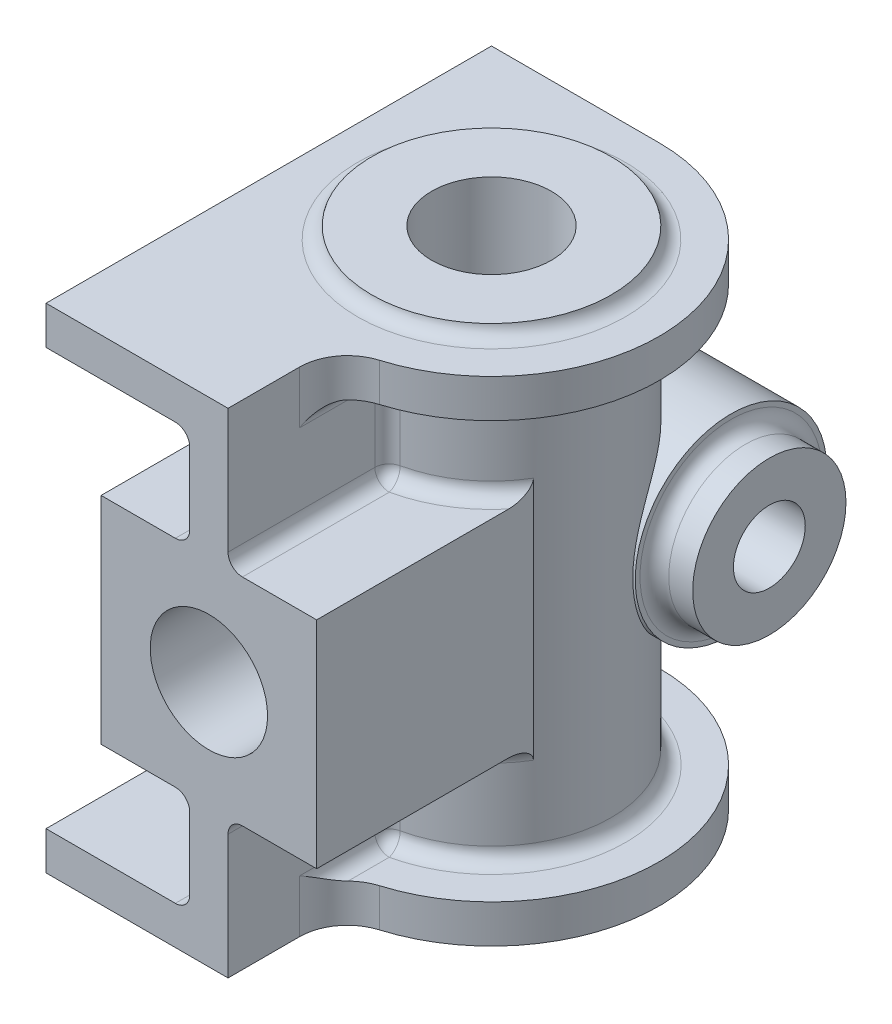
SolidWorks part; units mm, degrees
material "AISI 1020"
ref_plane "Front Plane" through (0, 0, 0) normal (1, 0, 0) x (0, 1, 0)
ref_plane "Top Plane" through (0, 0, 0) normal (0, 0, 1) x (0, 1, 0)
ref_plane "Right Plane" through (0, 0, 0) normal (0, 1, 0) x (-1, 0, 0)
sketch "Sketch1" plane through (0, 0, 0) normal (0, 1, 0) x (-1, 0, 0)
  line L0 (35, 0) -> (35, 58)
  line L1 (35, 58) -> (-3, 58)
  line L2 (35, 0) -> (35, -35)
  line L3 (0, -35) -> (35, -35)
  line L4 (-3, 58) -> (-3, 34.8712)
  line L5 (5, 58) -> (5, 34.641)
  circle A0 centre (0, 0) radius 12.5
  circle A1 centre (0, 0) radius 25
  circle A2 centre (0, 0) radius 35
  point P12 (5, 58)
  dimension "D1" = 25
  dimension "D2" = 50
  dimension "D3" = 70
  dimension "D4" = 58
  dimension "D5" = 38
  dimension "D6" = 8
extrude "Boss-Extrude1" add sketch "Sketch1" against normal blind 103 contours A2 A1 | A2 L0 L1 L5 | A2 L5 L1 L4 | A2 L3 L2 | A1 A0 region at (-21.9929, 0, 41.1744) region at (-24.0487, 0, -24.0487) region at (-27.1821, 0, -27.1821) region at (-1.0066, 0, 46.4544) region at (24.2929, 0, 0)
extrude "Boss-Extrude2" add sketch "Sketch1<4>" against normal blind 105.5 contours A1 A0 region at (24.2929, 0, 0)
sketch "Sketch1<4>" plane through (0, 0, 0) normal (0, 1, 0) x (-1, 0, 0) same geometry as "Sketch1"
extrude "Cut-Extrude1" cut sketch "Sketch1<6>" against normal blind 95 contours A2 L5 L1 L4 | A2 L0 L1 L5 | A2 L3 L2 | A2 A1 region at (-21.9929, 0, 41.1744) region at (-24.0487, 0, -24.0487) region at (-27.1821, 0, -27.1821) region at (-1.0066, 0, 46.4544)
sketch "Sketch1<6>" plane through (0, 0, 0) normal (0, 1, 0) x (-1, 0, 0) same geometry as "Sketch1"
extrude "Boss-Extrude3" add sketch "Sketch1<7>" against normal blind 8 contours A2 A1 | A2 L5 L1 L4 | A2 L0 L1 L5 | A2 L3 L2 region at (-21.9929, 0, 41.1744) region at (-24.0487, 0, -24.0487) region at (-27.1821, 0, -27.1821) region at (-1.0066, 0, 46.4544)
sketch "Sketch1<7>" plane through (0, 0, 0) normal (0, 1, 0) x (-1, 0, 0) same geometry as "Sketch1"
extrude "Boss-Extrude4" add sketch "Sketch1<8>" along normal blind 2.5 contours A1 A0 region at (24.2929, 0, 0)
sketch "Sketch1<8>" plane through (0, 0, 0) normal (0, 1, 0) x (-1, 0, 0) same geometry as "Sketch1"
sketch "Sketch2" plane through (0, 0, 58) normal (0, 0, 1) x (1, 0, 0)
  line L0 (-35, 0) -> (3, 0) construction
  line L1 (3, -103) -> (-5, -103)
  line L2 (3, -103) -> (3, 0)
  line L3 (3, 0) -> (-5, 0)
  line L4 (-5, -103) -> (-5, 0)
  line L5 (3, -51.5) -> (-5, -51.5) construction
  line L7 (21.5, -29) -> (-23.5, -29)
  line L8 (21.5, -29) -> (21.5, -74)
  line L9 (21.5, -74) -> (-23.5, -74)
  line L10 (-23.5, -29) -> (-23.5, -74)
  line L11 (21.5, -29) -> (-23.5, -74) construction
  line L12 (21.5, -74) -> (-23.5, -29) construction
  circle A0 centre (-1, -51.5) radius 11
  point P7 (-1, -51.5)
  line M11 (3, -95) -> (-35, -95)
  dimension "D4" = 22
  dimension "D1" = 8
  dimension "D2" = 45
  dimension "D3" = 45
extrude "Boss-Extrude6" add sketch "Sketch2" against normal up to next contours A0 L2 L9 L8 L7 | A0 L4 L9 L2 | A0 L4 L7 L10 L9 | L2 A0 L4 | L2 A0 | L4 A0 | A0 L2 L7 L4 | L2 L9 L4 M11 | L7 L2 L3 L4 region at (-1, -84.5, 58) region at (-1, -68.1241, 58) region at (13.1578, -51.5, 58) region at (-15.1578, -51.5, 58) region at (-1, -51.5, 58) region at (5.8939, -51.5, 58) region at (-7.8939, -51.5, 58) region at (-1, -34.8759, 58) region at (-1, -14.5, 58)
sketch "Sketch5" plane through (0, 0, 58) normal (0, 0, 1) x (1, 0, 0)
  point P0 (-1, -51.5)
hole_wizard "Tap Drill for M24 Helicoil1" positions "Sketch5" profile "Sketch6" hole size "M24x2.0" standard "BSI"
sketch "Sketch6" plane through (-1, -51.5, 58) normal (1, 0, 0) x (0, -1, 0)
  line L0 (0, 0) -> (0, 27.3605)
  line L1 (0, 27.3605) -> (12.25, 20)
  line L2 (12.25, 20) -> (12.25, 0)
  line L5 (12.25, 0) -> (0, 0)
  line L10 (0, 27.3605) -> (-12.25, 20) construction
  line L11 (0, -6.35) -> (0, 107.95) construction
  dimension "Hole Dia." = 24.5
  dimension "Hole Depth" = 20
  dimension "Drill Angle" = 118
sketch "Sketch9" plane through (0, 0, 58) normal (0, 0, 1) x (1, 0, 0)
  point P0 (-1, -51.5)
hole_wizard "Ø22.0 (22) Diameter Hole1" positions "Sketch9" profile "Sketch8" hole size "Ø22.0" standard "BSI"
sketch "Sketch8" plane through (-1, -51.5, 58) normal (1, 0, 0) x (0, -1, 0)
  line L0 (0, 0) -> (0, 38.6095)
  line L1 (0, 38.6095) -> (11, 32)
  line L2 (11, 32) -> (11, 0)
  line L5 (11, 0) -> (0, 0)
  line L10 (0, 38.6095) -> (-11, 32) construction
  line L11 (0, -6.35) -> (0, 107.95) construction
  dimension "Hole Dia." = 22
  dimension "Hole Depth" = 32
  dimension "Drill Angle" = 118
sketch "Sketch10" plane through (0, 0, 0) normal (1, 0, 0) x (0, 1, 0)
  line L0 (-95, -25) -> (-8, -25)
  circle A0 centre (-51.5, -25) radius 16
  circle A1 centre (-51.5, -25) radius 7.5
  circle A2 centre (-51.5, -25) radius 20
  dimension "D2" = 40
  dimension "D3" = 32
  dimension "D4" = 15
  dimension "D1" = 87
extrude "Boss-Extrude7" add sketch "Sketch10" along normal blind 25 and the other way blind 25 contours L0 A2 A0 | A1 L0 A0 | A1 L0 A0 | L0 A2 A0 region at (0, -51.5, -17.1935) region at (0, -51.5, -32.8065) region at (0, -51.5, -8.5528) region at (0, -33.5, -25.4472)
extrude "Boss-Extrude8" add sketch "Sketch10<5>" along normal blind 33 and the other way blind 33 contours A1 L0 A0 | A1 L0 A0 region at (0, -51.5, -17.1935) region at (0, -51.5, -32.8065)
sketch "Sketch10<5>" plane through (0, 0, 0) normal (1, 0, 0) x (0, 1, 0) same geometry as "Sketch10"
fillet "Fillet2" radius 3 2 edges at (-25, -51.5, -41) (25, -51.5, -41)
fillet "Fillet3" radius 3 2 edges at (0, 0, 25) (0, -103, 25)
fillet "Fillet4" radius 3 18 edges at (-5, -84.5, 24.4949) (-5, -18.5, 24.4949) (3, -8, 29.8453) (3, -95, 29.8453) (-16.3336, -74, 18.9265) (-16.3336, -29, 18.9265) (-5, -8, 41.2474) (-5, -29, 41.2474) (-5, -74, 41.2474) (-5, -95, 41.2474) (1.0131, -95, -24.9795) (1.0131, -8, -24.9795) (13.6541, -74, 20.9419) (3, -74, 41.4097) (3, -84.5, 24.8193) (3, -18.5, 24.8193) (3, -29, 41.4097) (13.6541, -29, 20.9419)
fillet "Fillet5" radius 10 2 edges at (3, -5.5, 34.8712) (3, -97.5, 34.8712)
